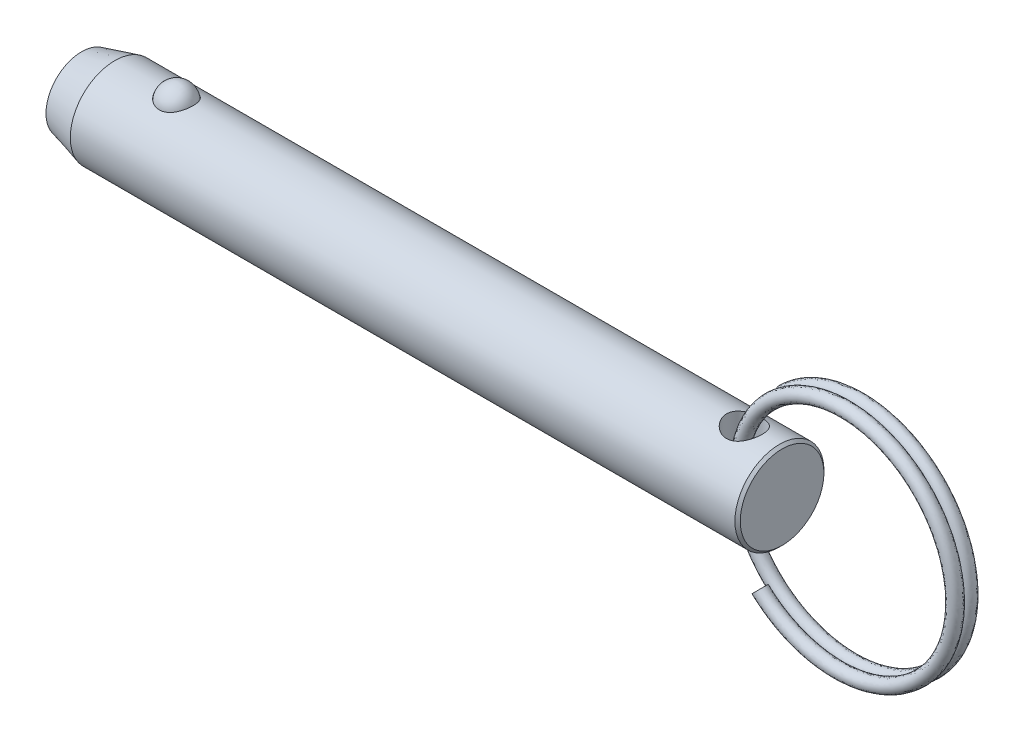
SolidWorks part; units mm, degrees
material "AISI 304"
ref_plane "Front" through (0, 0, 0) normal (0, 0, 1) x (1, 0, 0)
ref_plane "Top" through (0, 0, 0) normal (0, 1, 0) x (1, 0, 0)
ref_plane "Right" through (0, 0, 0) normal (1, 0, 0) x (0, 0, -1)
sketch "Sketch1" plane through (0, 0, 0) normal (0, 0, 1) x (1, 0, 0)
  line L0 (7.9248, 5.969) -> (7.5438, 6.35)
  line L1 (7.5438, 6.35) -> (7.9248, 6.35) construction
  line L4 (7.9248, 5.969) -> (7.9248, 0)
  line L5 (7.9248, 6.35) -> (7.9248, 5.969) construction
  line L16 (7.5438, 6.35) -> (-87.3353, 6.35)
  line L17 (-92.075, 6.35) -> (-92.075, 5.08) construction
  line L19 (-87.3353, 6.35) -> (-92.075, 6.35) construction
  line L22 (-92.075, -6.35) -> (-87.3353, -6.35) construction
  line L23 (-78.5279, 5.715) -> (-78.5279, -5.715) construction
  line L24 (-92.075, 0) -> (7.9248, 0)
  line L27 (7.9248, 0) -> (13.8938, 0) construction
  line L29 (-92.075, 0) -> (-92.075, -5.08) construction
  line L36 (0, 0) -> (0, 6.35) construction
  line L37 (-92.075, 5.08) -> (-92.075, 0)
  line L38 (-87.3353, -6.35) -> (7.9248, -6.35) construction
  line L39 (-92.075, -5.08) -> (-92.075, -6.35) construction
  line L40 (-87.3353, 6.35) -> (-92.075, 5.08)
  line L42 (-87.3353, -6.35) -> (-92.075, -5.08) construction
  line L43 (-87.3353, 6.35) -> (-87.3353, -6.35) construction
  circle A2 centre (-78.5279, 5.715) radius 2.413 construction
  point P35 (-76.2, 6.35)
  dimension "D2" = 11.43
  dimension "D11" = 1.778
  dimension "A" = 12.7
  dimension "D" = 7.9248
  dimension "E" = 14.478
  dimension "D3" = 0.381
  dimension "Useable Length" = 76.2
  dimension "D12" = 10.16
  dimension "C" = 15.875
  dimension "A1" = 15
revolve "Revolve1" add sketch "Sketch1" angle 360 about L27
sketch "Sketch2" plane through (0, 0, 0) normal (0, 0, 1) x (1, 0, 0)
  line L0 (-76.0895, 5.715) -> (-80.9663, 5.715)
  line L1 (-78.5279, 8.128) -> (-78.5279, 8.1534) construction
  line L2 (-76.0895, 5.715) -> (-71.2127, 5.715) construction
  circle A0 centre (-78.5279, 5.715) radius 2.413 construction
  circle A1 centre (-78.5279, 5.715) radius 2.413 construction
  arc A2 (-80.9663, 5.715) -> (-76.0895, 5.715) centre (-78.5279, 5.715) cw
  dimension "D1" = 0.0254
revolve "Cut-Revolve1" cut sketch "Sketch2" angle 360 about L2
sketch "Sketch3" plane through (0, 0, 0) normal (0, 0, 1) x (1, 0, 0)
  line L0 (-76.1149, 5.715) -> (-80.9409, 5.715)
  line L1 (-76.1149, 5.715) -> (-71.2889, 5.715) construction
  circle A0 centre (-78.5279, 5.715) radius 2.413 construction
  arc A1 (-76.1149, 5.715) -> (-80.9409, 5.715) centre (-78.5279, 5.715) ccw
revolve "Revolve2" add sketch "Sketch3" angle 360 about L1
sketch "Sketch4" plane through (0, 0, 0) normal (0, 0, 1) x (1, 0, 0)
  line L1 (2.54, -6.35) -> (5.08, -6.35)
  line L2 (2.54, -6.35) -> (2.54, 6.35)
  line L3 (2.54, 6.35) -> (5.08, 6.35)
  line L4 (5.08, -6.35) -> (5.08, 6.35)
  line L5 (2.54, -6.35) -> (2.54, -8.89) construction
  line L6 (5.08, 6.35) -> (7.9248, 6.35) construction
  line L8 (0, -6.35) -> (0, 6.35) construction
  line L9 (0, 0) -> (2.54, 0) construction
  line L11 (2.54, 0) -> (5.08, 0) construction
  line L12 (7.5438, 6.35) -> (-87.3353, 6.35) construction
  line L14 (-87.3353, -6.35) -> (7.9248, -6.35) construction
  dimension "D1" = 5.08
revolve "Cut-Revolve2" cut sketch "Sketch4" angle 360 about L2
sketch "Sketch5" plane through (0, 0, 0) normal (0, 0, 1) x (1, 0, 0)
  line L0 (0, 0) -> (0.8783, 0) construction
  line L1 (0.8783, 0) -> (0.8783, 6.35) construction
  line L2 (7.5438, 6.35) -> (-87.3353, 6.35) construction
  line L3 (17.7058, 0) -> (34.5333, 0) construction
  line L4 (5.08, 6.35) -> (4.2017, 6.35) construction
  line L5 (2.54, 6.35) -> (5.08, 6.35) construction
  line L6 (2.1224, 6.35) -> (2.1224, -6.35) construction
  line L7 (0.8783, 6.35) -> (0, 6.35) construction
  line L8 (2.54, -6.35) -> (5.08, -6.35) construction
  line L9 (2.1224, -6.35) -> (5.08, -6.35) construction
  line L10 (0.8783, 0) -> (17.7058, 0) construction
  line L11 (17.7058, 0) -> (11.3992, -13.5244) construction
  line L12 (4.2017, 6.35) -> (2.1224, 6.35) construction
  line L13 (17.7058, 14.9225) -> (17.7058, 16.8275) construction
  line L14 (11.3992, -13.5244) -> (10.9967, -14.3876) construction
  circle A0 centre (17.7058, 0) radius 16.8275
  circle A1 centre (17.7058, 0) radius 14.9225 construction
  circle A2 centre (17.7058, 0) radius 15.875 construction
  point P26 (17.7058, 15.875)
  dimension "D1" = 65
  dimension "R Ring Dia" = 31.75
  dimension "Ring OD" = 1.905
curve "Helix/Spiral1" pitch 1.9304 height 1.6891 radius 16.8275 left hand yes centre (17.7058, 0, 0) axis (0, 0, -1) start towards (1, 0, 0)
sketch "Sketch6" plane through (114.0038, 0, 0) normal (0, 1, 0) x (0, 0, -1)
  line L0 (0, 111.2206) -> (0, 112.1731) construction
  line L1 (0, 112.1731) -> (0, 113.1256) construction
  circle A0 centre (0, 112.1731) radius 0.9525
  dimension "D1" = 1.905
sketch "Sketch7" plane through (0, 0, 0) normal (0, 0, 1) x (1, 0, 0)
  circle A0 centre (17.7058, 0) radius 16.8275 construction
  circle A1 centre (17.7058, 0) radius 16.8275
curve "Helix/Spiral2" pitch 1.9304 height 1.6891 radius 16.8275 left hand yes centre (17.7058, 0, 0) axis (0, 0, 1) start towards (1, 0, 0)
sweep "Sweep1" add profiles "Sketch6" path "Helix/Spiral1"
sweep "Sweep2" add profiles "Sketch6<2>" path "Helix/Spiral2"
sketch "Sketch6<2>" plane through (114.0038, 0, 0) normal (0, 1, 0) x (0, 0, -1) same geometry as "Sketch6"
ref_plane "Plane1" through (0, -13.5244, 0) normal (0, 1, 0) x (-1, 0, 0)
sketch "Sketch8" plane through (0, -13.5244, 0) normal (0, 1, 0) x (-1, 0, 0)
  line L0 (293.4008, 0) -> (-11.3992, 0) construction
  line L1 (7.6508, -0.7779) -> (1.8172, -0.7779)
  line L2 (0.811, -0.9415) -> (-9.89, -4.517)
  line L3 (-9.89, 4.517) -> (0.811, 0.9415)
  line L4 (1.8172, 0.7779) -> (280.1844, 0.7779)
  line L5 (281.1905, 0.9415) -> (291.8915, 4.517)
  line L6 (274.3508, -0.7779) -> (280.1844, -0.7779)
  line L7 (281.1905, -0.9415) -> (291.8915, -4.517)
  line L8 (7.6508, -0.7779) -> (7.6508, 0.7779) construction
  arc A0 (-9.89, 4.517) -> (-9.89, -4.517) centre (-11.3992, 0) ccw
  arc A1 (291.8915, -4.517) -> (291.8915, 4.517) centre (293.4008, 0) ccw
  arc A2 (1.8172, -0.7779) -> (0.811, -0.9415) centre (1.8172, -3.9529) ccw
  arc A3 (0.811, 0.9415) -> (1.8172, 0.7779) centre (1.8172, 3.9529) ccw
  arc A4 (280.1844, -0.7779) -> (281.1905, -0.9415) centre (280.1844, -3.9529) cw
  arc A5 (280.1844, 0.7779) -> (281.1905, 0.9415) centre (280.1844, 3.9529) ccw
  point P6 (7.6508, 0)
  point P16 (1.3008, -0.7779)
  point P20 (1.3008, 0.7779)
  point P23 (280.7008, -0.7779)
  point P26 (280.7008, 0.7779)
  dimension "D2" = 4.7625
  dimension "D3" = 1.5557
  dimension "D6" = 3.175
  dimension "Lanyard Length" = 304.8
  dimension "D4" = 6.35
  dimension "D5" = 12.7
ref_plane "Plane2" through (-7.6508, 0, 0) normal (1, 0, 0) x (0, 0, -1)
sketch "Sketch9" plane through (-7.6508, 0, 0) normal (1, 0, 0) x (0, 0, -1)
  circle A0 centre (0.7779, -13.5244) radius 0.7779
sweep "Sweep3" [suppressed] add profiles "Sketch9" path "Sketch8"
sketch "Sketch10" [suppressed] plane through (-7.6508, 0, 0) normal (1, 0, 0) x (0, 0, -1)
  arc A0 (-0.3849, -12.853) -> (-0.3849, -14.1957) centre (-0.7779, -13.5244) ccw
  circle A1 centre (0.7779, -13.5244) radius 0.7779
  arc A2 (0.3849, -14.1957) -> (0.3849, -12.853) centre (0.7779, -13.5244) ccw
  arc A3 (-0.3849, -14.1957) -> (0.3849, -14.1957) centre (0, -14.8533) cw
  arc A4 (-0.3869, -12.035) -> (-0.3869, -15.0138) centre (-0.7779, -13.5244) ccw
  arc A5 (0.3869, -15.0138) -> (0.3869, -12.035) centre (0.7779, -13.5244) ccw
  circle A6 centre (-0.7779, -13.5244) radius 1.5399 construction
  circle A7 centre (-0.7779, -13.5244) radius 0.7779 construction
  arc A8 (-0.3849, -12.853) -> (0.3849, -12.853) centre (0, -12.1954) ccw
  arc A9 (-0.3869, -12.035) -> (0.3869, -12.035) centre (0, -10.5609) ccw
  arc A10 (0.3869, -15.0138) -> (-0.3869, -15.0138) centre (0, -16.4879) ccw
  point P4 (-0.034, -10.2746)
  point P8 (2.3178, -10.502)
  point P9 (0.762, -10.502)
  dimension "D3" = 1.524
  dimension "D4" = 0.762
  dimension "D2" = 0.762
  dimension "D1" = 0
extrude "Extrude1" [suppressed] add sketch "Sketch10" along normal blind 5.715 separate body
sketch "Sketch11" [suppressed] plane through (-274.3508, 0, 0) normal (1, 0, 0) x (0, 0, -1)
  arc A4 (-0.3849, -12.853) -> (-0.3849, -14.1957) centre (-0.7779, -13.5244) ccw
  arc A5 (0.3849, -14.1957) -> (-0.3849, -14.1957) centre (0, -14.8533) ccw
  arc A6 (0.3849, -14.1957) -> (0.3849, -12.853) centre (0.7779, -13.5244) ccw
  arc A7 (-0.3849, -12.853) -> (0.3849, -12.853) centre (0, -12.1954) ccw
  arc A8 (-0.3849, -12.853) -> (-0.3849, -14.1957) centre (-0.7779, -13.5244) ccw
  arc A9 (0.3849, -14.1957) -> (-0.3849, -14.1957) centre (0, -14.8533) ccw
  arc A10 (0.3849, -14.1957) -> (0.3849, -12.853) centre (0.7779, -13.5244) ccw
  arc A11 (-0.3849, -12.853) -> (0.3849, -12.853) centre (0, -12.1954) ccw
  arc A12 (-0.3869, -12.035) -> (-0.3869, -15.0138) centre (-0.7779, -13.5244) ccw
  arc A13 (0.3869, -15.0138) -> (-0.3869, -15.0138) centre (0, -16.4879) ccw
  arc A14 (0.3869, -15.0138) -> (0.3869, -12.035) centre (0.7779, -13.5244) ccw
  arc A15 (-0.3869, -12.035) -> (0.3869, -12.035) centre (0, -10.5609) ccw
  arc A16 (-0.3869, -12.035) -> (-0.3869, -15.0138) centre (-0.7779, -13.5244) ccw
  arc A17 (0.3869, -15.0138) -> (-0.3869, -15.0138) centre (0, -16.4879) ccw
  arc A18 (0.3869, -15.0138) -> (0.3869, -12.035) centre (0.7779, -13.5244) ccw
  arc A19 (-0.3869, -12.035) -> (0.3869, -12.035) centre (0, -10.5609) ccw
  dimension "D1" = 0
  dimension "D2" = 0
extrude "Extrude2" [suppressed] add sketch "Sketch11" against normal blind 5.715 separate body
sketch "Sketch12" plane through (0, -13.5244, 0) normal (0, 1, 0) x (-1, 0, 0)
  line L0 (324.1817, -5.2864) -> (318.6191, -5.2864) construction
  line L1 (324.1817, -5.9214) -> (307.8132, -5.9214)
  line L2 (324.1817, -5.9214) -> (324.1817, -4.6514)
  line L3 (324.1817, -4.6514) -> (308.0371, -4.6514)
  line L4 (307.8132, -5.9214) -> (308.0371, -4.6514) construction
  line L5 (307.8132, -5.9214) -> (292.4317, -0.3231)
  line L6 (318.6191, -5.2864) -> (307.9251, -5.2864) construction
  line L7 (308.0371, -4.6514) -> (292.8661, 0.8704)
  line L8 (292.4317, -0.3231) -> (292.8661, 0.8704)
  line L9 (307.9251, -5.2864) -> (297.876, -1.6289) construction
  line L10 (297.876, -1.6289) -> (292.6489, 0.2737) construction
  arc A0 (291.8915, -4.517) -> (291.8915, 4.517) centre (293.4008, 0) ccw construction
  dimension "D1" = 20
  dimension "D2" = 31.75
  dimension "D3" = 1.27
  dimension "D4" = 5.5626
extrude "Extrude3" [suppressed] add sketch "Sketch12" along normal mid plane 12.7 separate body
sketch "Sketch13" [suppressed] plane through (0, 0, -4.6514) normal (0, 0, 1) x (1, 0, 0)
  line L0 (-324.1817, -13.5244) -> (-308.0371, -13.5244) construction
  line L1 (-322.1887, -7.1744) -> (-324.1817, -7.1744)
  line L2 (-324.1817, -7.1744) -> (-308.0371, -7.1744) construction
  line L3 (-324.1817, -7.1744) -> (-326.1747, -7.1744)
  line L4 (-326.1747, -7.1744) -> (-326.1747, -19.8744)
  line L5 (-326.1747, -19.8744) -> (-324.1817, -19.8744)
  line L6 (-324.1817, -19.8744) -> (-322.1887, -19.8744)
  line L7 (-324.1817, -19.8744) -> (-308.0371, -19.8744) construction
  arc A0 (-322.1887, -7.1744) -> (-322.1887, -19.8744) centre (-313.0692, -13.5244) ccw
  circle A1 centre (-318.6191, -13.5244) radius 2.5781
  dimension "D1" = 5.1562
  dimension "D2" = 11.1125
extrude "Extrude4" [suppressed] cut sketch "Sketch13" against normal up to surface (1.27 mm away)
sketch "Sketch14" [suppressed] plane through (-34.5386, 0, 94.8939) normal (-0.342, 0, 0.9397) x (0.9397, 0, 0.342)
  line L3 (-276.8994, -7.1744) -> (-274.9064, -7.1744)
  line L4 (-274.9064, -7.1744) -> (-272.9134, -7.1744)
  line L5 (-272.9134, -7.1744) -> (-272.9134, -19.8744)
  line L6 (-272.9134, -19.8744) -> (-274.9064, -19.8744)
  line L7 (-274.9064, -19.8744) -> (-276.8994, -19.8744)
  line L8 (-274.9064, -7.1744) -> (-274.9064, -19.8744) construction
  line L9 (-291.0511, -7.1744) -> (-274.9064, -7.1744) construction
  line L10 (-291.163, -13.5244) -> (-280.469, -13.5244) construction
  arc A0 (-276.8994, -19.8744) -> (-276.8994, -7.1744) centre (-286.0189, -13.5244) ccw
  circle A1 centre (-280.469, -13.5244) radius 2.5781
  dimension "D1" = 5.1562
  dimension "D2" = 11.1125
extrude "Extrude6" [suppressed] cut sketch "Sketch14" against normal up to surface (1.27 mm away)
sketch "Sketch15" [suppressed] plane through (0, 0, 0) normal (0, 0, 1) x (1, 0, 0)
  line L1 (-255.1191, -7.1744) -> (-96.3691, -7.1744)
  line L2 (-255.1191, -7.1744) -> (-267.8191, -19.8744)
  line L3 (-267.8191, -19.8744) -> (-109.0691, -19.8744)
  line L4 (-96.3691, -7.1744) -> (-109.0691, -19.8744)
  line L5 (-322.1887, -7.1744) -> (-308.0371, -7.1744) construction
  line L6 (-322.1887, -19.8744) -> (-308.0371, -19.8744) construction
  circle A0 centre (-318.6191, -13.5244) radius 2.5781 construction
  dimension "D1" = 63.5
  dimension "D2" = 158.75
  dimension "D3" = 45
extrude "Extrude7" [suppressed] cut sketch "Sketch15" against normal through all and the other way through all
move or copy body "Body-Move/Copy1" [suppressed] bodies to move or copy 147 151 144 copy no translate (152.4, 0, 0)
sketch "Sketch16" [suppressed] plane through (0, 0, 0) normal (0, 0, 1) x (1, 0, 0)
  line L0 (-109.0691, -8.7619) -> (-109.0691, -11.9369) construction
  line L1 (-109.0691, -11.9369) -> (-106.5291, -10.9844) construction
  line L2 (-106.5291, -10.9844) -> (-111.6091, -16.0644) construction
  line L3 (-111.6091, -16.0644) -> (-109.0691, -15.1119) construction
  line L4 (-109.0691, -15.1119) -> (-109.0691, -18.2869) construction
  line L5 (-109.847, -14.3023) -> (-108.2913, -12.7465) construction
  line L6 (-102.7191, -18.2869) -> (-102.7191, -15.1119) construction
  line L7 (-102.7191, -15.1119) -> (-105.2591, -16.0644) construction
  line L8 (-105.2591, -16.0644) -> (-100.1791, -10.9844) construction
  line L9 (-100.1791, -10.9844) -> (-102.7191, -11.9369) construction
  line L10 (-102.7191, -11.9369) -> (-102.7191, -8.7619) construction
  line L11 (-101.9413, -12.7465) -> (-103.497, -14.3023) construction
  line L14 (-1.8172, -13.5244) -> (-280.1844, -13.5244) construction
  dimension "D1" = 3.175
  dimension "D2" = 3.175
  dimension "D3" = 5.08
  dimension "D4" = 1.5875
equation "\"D12@Sketch1\"=\"A@Sketch1\" * 0.80"
equation "\"D2@Sketch1\"=\"A@Sketch1\" * 0.9"
equation "\"D1@Sketch4\" = \"A@Sketch1\" / 2.5"
equation "\"Ring OD@Sketch5\" = \"R Ring Dia@Sketch5\" * 0.06"
equation "\"D4@Helix/Spiral1\"=\"Ring OD@Sketch5\" + 0.001"
equation "\"D1@Sketch6\"=\"Ring OD@Sketch5\""
equation "\"D4@Helix/Spiral2\" = \"D4@Helix/Spiral1\""
equation "\"D5@Helix/Spiral2\" = \"D5@Helix/Spiral1\""
equation "\"D1@Sketch14\" = \"D1@Sketch13\""
equation "\"D2@Sketch14\" = \"D2@Sketch13\""
